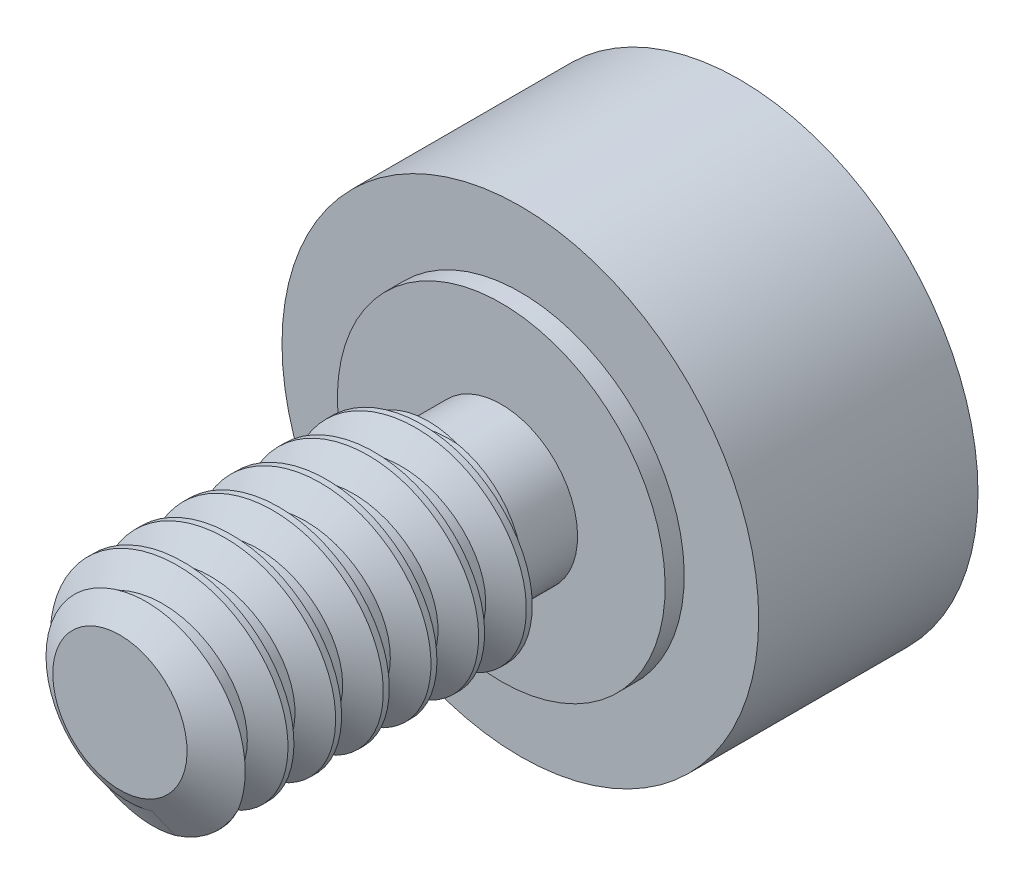
SolidWorks part; units mm, degrees
material "Plain Carbon Steel"
ref_plane "Front Plane" through (0, 0, 0) normal (0, 0, 1) x (1, 0, 0)
ref_plane "Top Plane" through (0, 0, 0) normal (0, 1, 0) x (1, 0, 0)
ref_plane "Right Plane" through (0, 0, 0) normal (1, 0, 0) x (0, 0, -1)
sketch "Sketch1" plane through (0, 0, 0) normal (1, 0, 0) x (0, 0, -1)
  line L0 (-5.334, 0) -> (2.921, 0)
  line L1 (2.921, 0) -> (2.921, 3.175)
  line L2 (2.921, 3.175) -> (0, 3.175)
  line L3 (0, 3.175) -> (0, 2.1828)
  line L4 (0, 2.1828) -> (-0.254, 2.1828)
  line L5 (-0.254, 2.1828) -> (-0.254, 1.016)
  line L6 (-0.254, 1.016) -> (-1.0477, 1.016)
  line L7 (-1.0477, 1.016) -> (-1.0477, 1.4224)
  line L8 (-1.0477, 1.4224) -> (-5.334, 1.4224)
  line L9 (-5.334, 1.4224) -> (-5.334, 0)
  line L10 (2.921, 0) -> (-5.334, 0) construction
  point P4 (0, 0)
  point P12 (0, 3.175)
  point P13 (0, 3.175)
  point P14 (5.3698, 3.175)
  point P15 (2.3813, 3.3976)
  dimension "D1" = 1.4224
  dimension "D2" = 3.175
  dimension "D3" = 5.08
  dimension "D4" = 0.7937
  dimension "D5" = 1.016
  dimension "D6" = 2.1828
  dimension "D7" = 0.254
  dimension "D8" = 3.175
revolve "Revolve1" add sketch "Sketch1" angle 360 about L0
chamfer "Chamfer1" distance 0.3048 angle 60 1 edges at (0, -1.4224, 5.334) first distance on face at (0, -1.4224, 5.334)
thread "Thread1" pitch 0.635 method cut profile "Thread Profile1" start angle 0, offset 1, length 0, pitch 0.635, diameter 2.8448
ref_plane "Plane1" through (-1.4224, 0, 6.0292) normal (0, -1, 0) x (-1, 0, 0)
sketch "Thread Profile1" plane through (-1.4224, 0, 6.0292) normal (0, -1, 0) x (-1, 0, 0)
  line L0 (0, 0) -> (0, 0.635) construction
  line L11 (0, 0) -> (0, 0.5556)
  line L12 (0, 0.5556) -> (-0.3437, 0.3572)
  line L13 (-0.3437, 0.3572) -> (-0.3437, 0.1984)
  line L15 (-0.3437, 0.1984) -> (0, 0)
  line L17 (-0.3437, 0.2778) -> (0, 0.2778) construction
  point P2 (0, 0)
  dimension "Pitch" = 0.635
  dimension "Profile_Angle" = 60
  dimension "Profile_Land" = 0.1588
  dimension "Profile_Height" = 0.3437
